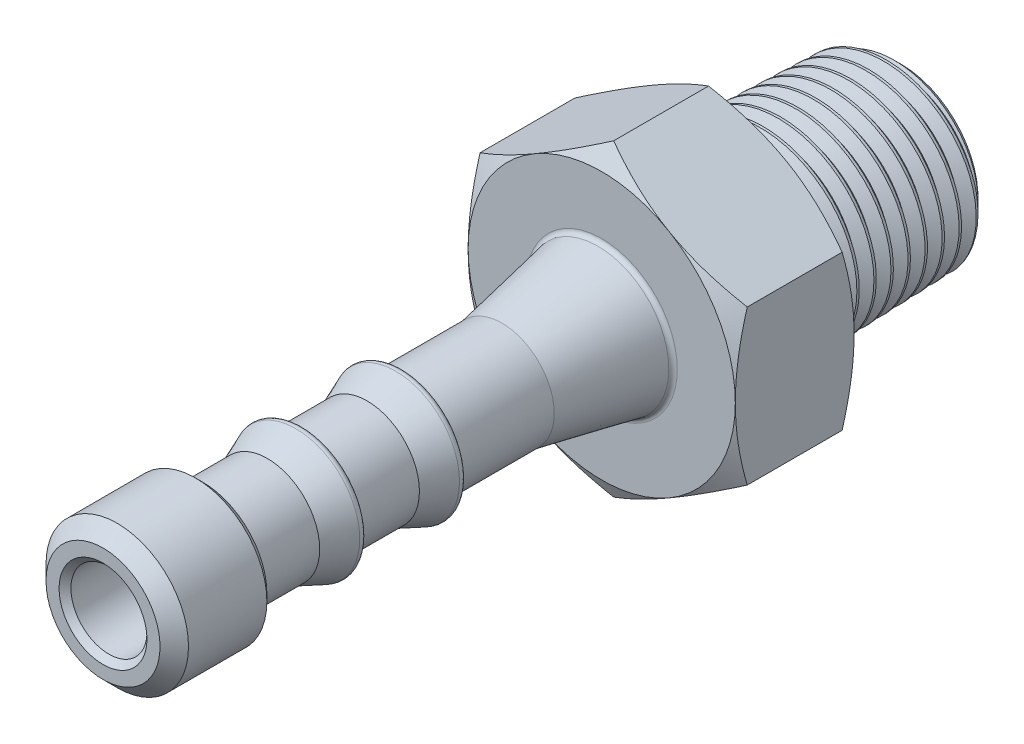
SolidWorks part; units mm, degrees
ref_plane "Front Plane" through (0, 0, 0) normal (0, 0, 1) x (1, 0, 0)
ref_plane "Top Plane" through (0, 0, 0) normal (0, 1, 0) x (1, 0, 0)
ref_plane "Right Plane" through (0, 0, 0) normal (1, 0, 0) x (0, 0, -1)
sketch "Sketch1" plane through (0, 0, 0) normal (1, 0, 0) x (0, 0, -1)
  line L0 (-26.67, 0) -> (0, 0) construction
  line L1 (0, 0) -> (6.35, 0) construction
  line L2 (6.35, 0) -> (16.002, 0) construction
  line L3 (-26.67, 3.175) -> (-26.67, -3.175) construction
  line L5 (0, 7.1437) -> (0, -7.1437) construction
  line L6 (-26.67, 2.032) -> (-26.67, -2.032) construction
  line L7 (-26.67, 3.81) -> (-26.67, -3.81) construction
  line L8 (6.35, 7.1437) -> (6.35, -7.1437) construction
  line L9 (16.002, 3.175) -> (16.002, -3.175) construction
  line L10 (6.035, -5.1435) -> (6.035, 5.1435) construction
  line L11 (6.035, 5.1435) -> (16.002, 4.8332) construction
  line L12 (16.002, 4.8332) -> (16.002, -4.8332) construction
  line L13 (6.035, 5.1435) -> (6.9758, 5.1435) construction
  point P26 (6.035, 0)
  dimension "Hose ID" = 6.35
  dimension "Pipe OD" = 10.287
  dimension "Length" = 42.672
  dimension "Hex" = 14.2875
  dimension "Thread Length" = 9.652
  dimension "Barb End Length" = 26.67
  dimension "Barb ID" = 4.064
  dimension "Barb OD" = 7.62
  dimension "L4" = 9.967
  dimension "Taper" = 1.783
  dimension "Pitch" = 0.9407
  dimension "Pipe ID" = 6.35
sketch "Sketch2" plane through (0, 0, 0) normal (1, 0, 0) x (0, 0, -1)
  line L1 (-21.082, 2.794) -> (-17.8771, 2.794)
  line L2 (0, 4.0402) -> (0, 0)
  line L3 (0, 7.1437) -> (0, -7.1437) construction
  line L4 (-26.67, 0) -> (0, 0)
  line L7 (-26.67, 0) -> (-26.67, 3.81)
  line L9 (-26.67, 0) -> (0, 0) construction
  line L14 (-21.336, 3.048) -> (-21.336, 3.81)
  line L15 (-21.336, 3.81) -> (-26.67, 3.81)
  line L18 (-26.67, 7.1437) -> (-21.336, 7.1437) construction
  line L19 (-21.336, 7.1437) -> (-16.002, 7.1437) construction
  line L20 (-16.002, 7.1437) -> (-10.668, 7.1437) construction
  line L21 (-10.668, 7.1437) -> (-5.334, 7.1437) construction
  line L22 (-5.334, 7.1437) -> (0, 7.1437) construction
  line L23 (-26.67, 0) -> (-26.67, 7.1437) construction
  line L24 (-17.8771, 2.794) -> (-16.3512, 3.4105)
  line L25 (-16.002, 3.175) -> (-16.002, 3.048)
  line L26 (-15.748, 2.794) -> (-12.5431, 2.794)
  line L27 (-12.5431, 2.794) -> (-11.0172, 3.4105)
  line L28 (-10.668, 3.175) -> (-10.668, 3.048)
  line L29 (-10.414, 2.794) -> (-5.334, 2.794)
  line L30 (-5.334, 2.794) -> (-0.2055, 3.7909)
  line L38 (-16.256, 3.429) -> (-10.922, 3.429) construction
  arc A0 (-16.3512, 3.4105) -> (-16.002, 3.175) centre (-16.256, 3.175) cw
  arc A1 (-16.002, 3.048) -> (-15.748, 2.794) centre (-15.748, 3.048) ccw
  arc A2 (-11.0172, 3.4105) -> (-10.668, 3.175) centre (-10.922, 3.175) cw
  arc A3 (-10.668, 3.048) -> (-10.414, 2.794) centre (-10.414, 3.048) ccw
  arc A8 (-21.336, 3.048) -> (-21.082, 2.794) centre (-21.082, 3.048) ccw
  arc A10 (-0.2055, 3.7909) -> (0, 4.0402) centre (-0.254, 4.0402) ccw
  point P39 (-16.002, 2.794)
  point P44 (-10.668, 2.794)
  point P66 (-21.336, 2.794)
  dimension "D2" = 0.254
  dimension "D5" = 0.254
  dimension "D6" = 0.254
  dimension "D1" = 22
  dimension "D3" = 1.016
  dimension "D4" = 11
  dimension "D7" = 0.635
revolve "Revolve1" add sketch "Sketch2" angle 360 about L9
chamfer "Chamfer1" distance 0.381 angle 45 1 edges at (3.81, 0, 21.336)
chamfer "Chamfer2" distance 0.762 angle 45 1 edges at (3.81, 0, 26.67)
ref_plane "Plane1" through (0, 0, -16.002) normal (0, 0, 1) x (1, 0, 0)
sketch "Sketch3" plane through (0, 0, -16.002) normal (0, 0, 1) x (1, 0, 0)
  circle A0 centre (0, 0) radius 4.8332
extrude "Boss-Extrude1" add sketch "Sketch3" along normal up to vertex (9.652 mm away) draft 1.783 separate body up to point (0, 0, -6.35) draft outward yes
sketch "Sketch4" plane through (0, 0, -16.002) normal (0, 0, -1) x (-1, 0, 0)
  circle A1 centre (0, 0) radius 4.8332
  circle A2 centre (0, 0) radius 4.8332
  point P0 (0, 4.8332)
  dimension "D1" = 0
curve "Helix/Spiral1"
sketch "Sketch5" plane through (0, 0, 0) normal (1, 0, 0) x (0, 0, -1)
  line L0 (15.9432, 4.935) -> (16.8839, 4.935) construction
  line L1 (16.8839, 4.935) -> (16.4136, 4.1203) construction
  line L2 (16.4136, 4.1203) -> (15.9432, 4.935) construction
  line L3 (16.3548, 4.2221) -> (16.4724, 4.2221) construction
  line L4 (16.002, 4.8332) -> (16.8251, 4.8332) construction
  line L5 (16.4136, 4.1203) -> (16.4136, 4.2221) construction
  line L6 (16.4136, 4.8332) -> (16.4136, 4.935) construction
  line L7 (16.4136, 4.8841) -> (16.8545, 4.8841) construction
  line L8 (16.8545, 4.8841) -> (15.9432, 4.935)
  line L9 (15.9432, 4.935) -> (16.3548, 4.2221)
  line L10 (16.3548, 4.2221) -> (16.4724, 4.2221)
  line L11 (16.4724, 4.2221) -> (16.8545, 4.8841)
  line L12 (16.4136, 4.1203) -> (16.4136, -4.8204) construction
  line L13 (16.4136, -4.8204) -> (15.4733, -4.8496) construction
  line L14 (15.4733, -4.8496) -> (14.533, -4.8789) construction
  line L15 (14.533, -4.8789) -> (13.5927, -4.9082) construction
  line L16 (13.5927, -4.9082) -> (12.6524, -4.9375) construction
  line L17 (6.35, -5.1337) -> (16.002, -4.8332) construction
  dimension "D1" = 0.9407
  dimension "D2" = 0.1176
sweep "Cut-Sweep1" cut profiles "Sketch5" path "Helix/Spiral1"
sketch "Sketch6" plane through (0, 0, -16.002) normal (0, 0, -1) x (-1, 0, 0)
  circle A0 centre (0, 0) radius 4.1203
extrude "Cut-Extrude1" cut sketch "Sketch6" against normal up to vertex (9.652 mm away) draft 45 flip side to cut up to point (0, 0, -6.35)
sketch "Sketch7" plane through (0, 0, 0) normal (0, 0, -1) x (-1, 0, 0)
  line L1 (0, 8.2489) -> (-7.1437, 4.1244)
  line L2 (-7.1437, 4.1244) -> (-7.1437, -4.1244)
  line L3 (-7.1437, -4.1244) -> (0, -8.2489)
  line L4 (0, -8.2489) -> (7.1437, -4.1244)
  line L5 (7.1437, -4.1244) -> (7.1438, 4.1244)
  line L6 (7.1438, 4.1244) -> (0, 8.2489)
  circle A0 centre (0, 0) radius 7.1438 construction
extrude "Boss-Extrude2" add sketch "Sketch7" along normal up to vertex (6.35 mm away) up to point (0, 0, -6.35)
sketch "Sketch8" plane through (0, 0, 0) normal (0, 0, 1) x (1, 0, 0)
  circle A0 centre (0, 0) radius 7.1438 construction
  circle A1 centre (0, 0) radius 7.1438
extrude "Cut-Extrude2" cut sketch "Sketch8" against normal up to vertex (6.35 mm away) draft 60 flip side to cut up to point (0, 0, -6.35)
sketch "Sketch9" plane through (0, 0, -6.35) normal (0, 0, -1) x (-1, 0, 0)
  circle A1 centre (0, 0) radius 7.1438
  circle A2 centre (0, 0) radius 7.1438
  dimension "D1" = 0
extrude "Cut-Extrude3" cut sketch "Sketch9" against normal up to vertex (6.35 mm away) draft 60 flip side to cut up to point (0, 0, 0)
sketch "Sketch10" plane through (0, 0, 0) normal (1, 0, 0) x (0, 0, -1)
  line L0 (0, 0) -> (-26.67, 0) construction
  line L1 (-26.67, 2.032) -> (6.35, 2.032)
  line L2 (-26.67, 2.032) -> (-26.67, 0)
  line L3 (-26.67, 0) -> (6.35, 0)
  line L4 (6.35, 2.032) -> (6.35, 0)
revolve "Cut-Revolve1" cut sketch "Sketch10" angle 360 about L0
chamfer "Chamfer3" distance 0.3175 angle 45 1 edges at (-2.032, 0, 26.67)
sketch "Sketch11" plane through (0, 0, 0) normal (1, 0, 0) x (0, 0, -1)
  line L0 (0, 0) -> (16.002, 0) construction
  line L1 (0, 7.1437) -> (0, -7.1437) construction
  line L2 (16.002, 0) -> (16.002, 3.175)
  line L3 (16.002, 3.175) -> (6.35, 3.175)
  line L4 (6.35, 3.175) -> (4.4423, 0)
  line L5 (4.4423, 0) -> (16.002, 0)
  line L6 (6.35, 7.1437) -> (6.35, -7.1437) construction
  dimension "D1" = 59
revolve "Cut-Revolve2" cut sketch "Sketch11" angle 360 about L0
chamfer "Chamfer4" distance 0.508 angle 45 1 edges at (3.175, 0, -16.002)
equation "\"D3@Boss-Extrude1\" = \"Taper@Sketch1\""
equation "\"D6@Helix/Spiral1\" = \"Taper@Sketch1\""
equation "\"D4@Helix/Spiral1\" = \"Pitch@Sketch1\""
equation "\"D3@Helix/Spiral1\" = \"D4@Helix/Spiral1\" + \"L4@Sketch1\""
equation "\"D1@Sketch5\" = \"D4@Helix/Spiral1\""
equation "\"D2@Sketch5\" = \"D1@Sketch5\" / 8"
